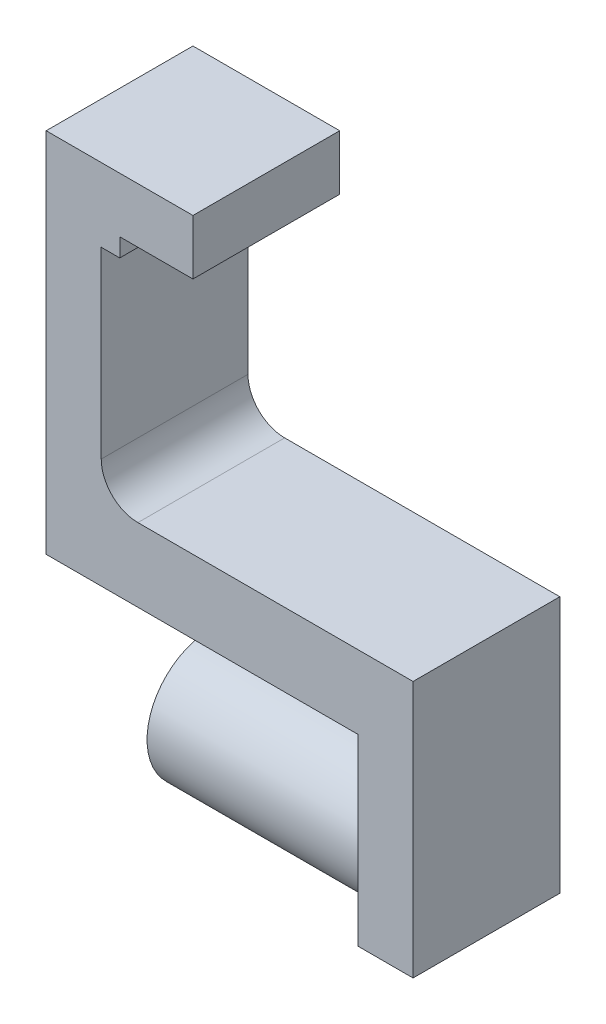
SolidWorks part; units mm, degrees
material "ASTM A36 Steel"
ref_plane "Front Plane" through (0, 0, 0) normal (0, 0, 1) x (1, 0, 0)
ref_plane "Top Plane" through (0, 0, 0) normal (0, 1, 0) x (1, 0, 0)
ref_plane "Right Plane" through (0, 0, 0) normal (1, 0, 0) x (0, 0, -1)
sketch "Sketch1" plane through (0, 0, 0) normal (1, 0, 0) x (0, 0, -1)
  circle A0 centre (0, 0) radius 11.1125
  dimension "D1" = 22.225
extrude "Boss-Extrude1" add sketch "Sketch1" against normal blind 38.1
sketch "Sketch2" plane through (0, 0, 0) normal (0, 0, 1) x (1, 0, 0)
  line L1 (0, -11.1125) -> (9.525, -11.1125)
  line L2 (0, -11.1125) -> (0, 20.6375)
  line L3 (0, 20.6375) -> (9.525, 20.6375)
  line L4 (9.525, -11.1125) -> (9.525, 20.6375)
  dimension "D1" = 9.525
  dimension "D2" = 31.75
  dimension "D3" = 11.1125
extrude "Boss-Extrude2" add sketch "Sketch2" along normal blind 12.7 and the other way blind 12.7
sketch "Sketch3" plane through (0, 0, 0) normal (0, 0, 1) x (1, 0, 0)
  line L1 (-53.975, 20.6375) -> (9.525, 20.6375)
  line L2 (-53.975, 20.6375) -> (-53.975, 33.3375)
  line L3 (-53.975, 33.3375) -> (9.525, 33.3375)
  line L4 (9.525, 20.6375) -> (9.525, 33.3375)
  dimension "D1" = 63.5
  dimension "D2" = 12.7
  dimension "D3" = 20.6375
  dimension "D4" = 53.975
extrude "Boss-Extrude3" add sketch "Sketch3" along normal blind 12.7 and the other way blind 12.7
sketch "Sketch4" plane through (0, 0, 0) normal (0, 0, 1) x (1, 0, 0)
  line L1 (-53.975, 20.6375) -> (-44.45, 20.6375)
  line L2 (-53.975, 20.6375) -> (-53.975, 84.1375)
  line L3 (-53.975, 84.1375) -> (-44.45, 84.1375)
  line L4 (-44.45, 20.6375) -> (-44.45, 84.1375)
  dimension "D3" = 20.6375
  dimension "D4" = 53.975
  dimension "D1" = 9.525
  dimension "D2" = 63.5
extrude "Boss-Extrude4" add sketch "Sketch4" along normal blind 12.7 and the other way blind 12.7
sketch "Sketch5" plane through (0, 0, 0) normal (0, 0, 1) x (1, 0, 0)
  line L5 (-53.975, 71.4375) -> (-41.2394, 71.4375)
  line L6 (-53.975, 84.1375) -> (-53.975, 20.6375) construction
  line L7 (-41.2394, 71.4375) -> (-41.2394, 74.6125)
  line L8 (-41.2394, 74.6125) -> (-28.575, 74.6125)
  line L9 (-28.575, 74.6125) -> (-28.575, 84.1375)
  line L10 (-28.575, 84.1375) -> (-53.975, 84.1375)
  line L11 (-53.975, 84.1375) -> (-53.975, 71.4375)
  dimension "D1" = 12.7
  dimension "D2" = 3.175
  dimension "D3" = 12.6644
  dimension "D4" = 25.4
  dimension "D5" = 84.1375
  dimension "D6" = 53.975
extrude "Boss-Extrude5" add sketch "Sketch5" along normal blind 12.7 and the other way blind 12.7
fillet "Fillet1" radius 6.35 1 edges at (-44.45, 33.3375, 0)
equation "\"F\"= 700"
equation "\"SF\"= 4"
equation "\"Sy\"= 36000"
equation "\"E\"= 29000000"
equation "\"dmax\"= 0.005"
equation "\"LA\"= 1.5"
equation "\"LB\"= 1.25"
equation "\"LC\"= 2.5"
equation "\"LD\"= 1.5"
equation "\"LE\"= 1"
equation "\"W\"= 1"
equation "\"tprac\"= 0.375"
equation "\"step\"= 0.125"
equation "\"slotW\"= 0.4986"
equation "\"slotD\"= 0.125"
equation "\"P\"= \"F\" / 2"
equation "\"sigA\"= \"Sy\" / \"SF\""
equation "\"MA\"= \"P\" * \"LA\""
equation "\"dAmin\"= ( 32 * \"MA\" / ( pi * \"sigA\" ) ) ^ ( 1 / 3 )"
equation "\"dA\"= ( int( \"dAmin\" / \"step\" ) + 1 ) * \"step\""
equation "\"MC\"= \"P\" * \"LC\" / 4"
equation "\"hCmin\"= sqr( 6 * \"MC\" / ( \"W\" * \"sigA\" ) )"
equation "\"hC\"= 0.5"
equation "\"ME\"= ( \"P\" / 2 ) * \"LE\""
equation "\"hEmin\"= sqr( 6 * \"ME\" / ( \"W\" * \"sigA\" ) )"
equation "\"hE\"= ( int( ( \"hEmin\" + \"slotD\" ) / \"step\" ) + 1 ) * \"step\""
equation "\"tB\"= \"tprac\""
equation "\"tD\" = \"tprac\""
equation "\"yb\"= \"LB\" - \"dA\" / 2"
equation "\"hD\"= \"hC\" + \"LD\" + \"hE\""
equation "\"yD\"= \"yb\" + \"hD\""
equation "\"xl\"= \"LC\" - \"tB\""
equation "\"D1@Sketch1\" = \"dA\""
equation "\"D1@Sketch2\" = \"tB\""
equation "\"D2@Sketch2\" = \"LB\""
equation "\"D3@Sketch2\" = \"dA\" / 2"
equation "\"D1@Sketch3\" = \"LC\""
equation "\"D2@Sketch3\" = \"hC\""
equation "\"D3@Sketch3\" = \"yb\""
equation "\"D4@Sketch3\" = \"xl\""
equation "\"D1@Sketch4\" = \"tD\""
equation "\"D2@Sketch4\" = \"hD\""
equation "\"D1@Sketch5\" = \"hE\""
equation "\"D2@Sketch5\" = \"slotD\""
equation "\"D3@Sketch5\" = \"slotW\""
equation "\"D4@Sketch5\" = \"LE\""
equation "\"D5@Sketch5\"= \"yD\""
